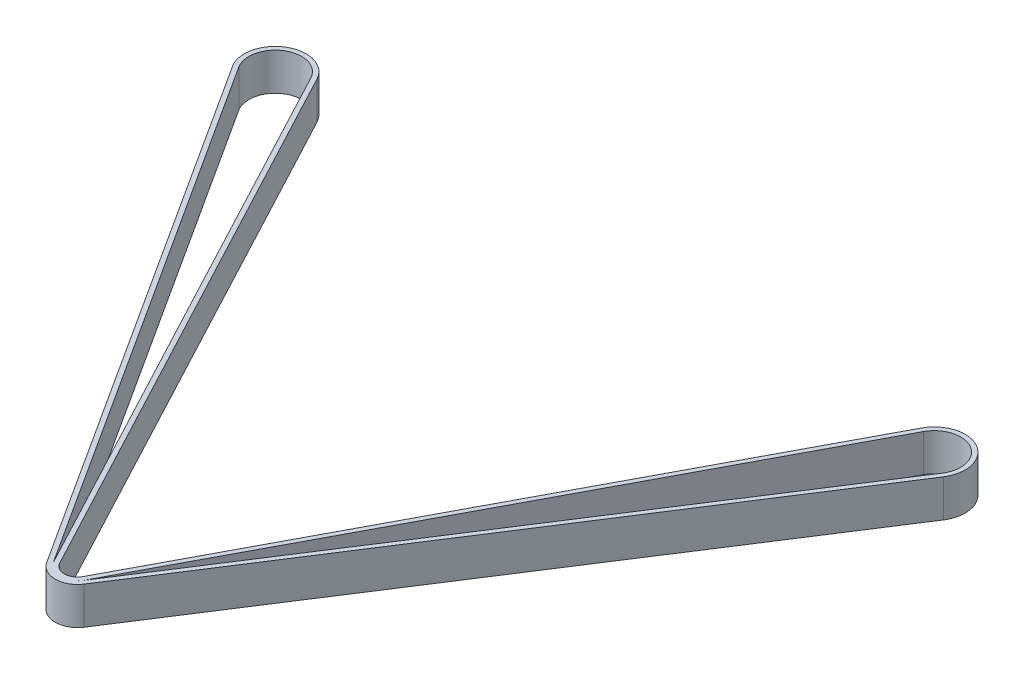
SolidWorks part; units mm, degrees
ref_plane "Front" through (0, 0, 0) normal (0, 0, 1) x (1, 0, 0)
ref_plane "Top" through (0, 0, 0) normal (0, 1, 0) x (1, 0, 0)
ref_plane "Right" through (0, 0, 0) normal (1, 0, 0) x (0, 0, -1)
ref_axis "X" through (-80.9, 0, 0) along (1, 0, 0)
ref_axis "Y" through (0, -50, 0) along (0, 1, 0)
ref_axis "Z" through (0, 0, -80.9) along (0, 0, 1)
sketch "Sketch1" plane through (0, 0, 0) normal (0, 1, 0) x (1, 0, 0)
  line L0 (-50, 0) -> (50, 0) construction
  line L1 (0, 0) -> (0, -80) construction
  line L2 (-46.1614, 2.0358) -> (-2.0717, -81.0987) construction
  line L3 (2.0717, -81.0987) -> (46.1614, 2.0358) construction
  line L4 (53.6522, -2.3537) -> (2.5519, -81.6446) construction
  line L5 (-2.5519, -81.6446) -> (-53.6522, -2.3537) construction
  line L6 (-2.8419, -81.8315) -> (-53.9422, -2.5406)
  line L7 (-45.8566, 2.1974) -> (-1.7669, -80.9371)
  line L8 (1.7669, -80.9371) -> (45.8566, 2.1974)
  line L9 (53.9422, -2.5406) -> (2.8419, -81.8315)
  line L10 (-2.262, -81.4578) -> (-53.3623, -2.1669)
  line L11 (-46.4662, 1.8741) -> (-2.3765, -81.2603)
  line L12 (2.3765, -81.2603) -> (46.4662, 1.8741)
  line L13 (53.3623, -2.1669) -> (2.262, -81.4578)
  line L14 (0, -82.69) -> (0, -82.691) construction
  circle A0 centre (-50, 0) radius 4 construction
  circle A1 centre (50, 0) radius 4 construction
  arc A2 (-46.1614, 2.0358) -> (-53.6522, -2.3537) centre (-50, 0) ccw construction
  arc A3 (53.6522, -2.3537) -> (46.1614, 2.0358) centre (50, 0) ccw construction
  circle A4 centre (0, -80) radius 2 construction
  arc A5 (-2.0717, -81.0987) -> (2.0717, -81.0987) centre (0, -80) ccw construction
  arc A6 (-2.5519, -81.6446) -> (2.5519, -81.6446) centre (0, -80) ccw construction
  arc A7 (-45.8566, 2.1974) -> (-53.9422, -2.5406) centre (-50, 0) ccw
  arc A8 (-1.7669, -80.9371) -> (1.7669, -80.9371) centre (0, -80) ccw
  arc A9 (53.9422, -2.5406) -> (45.8566, 2.1974) centre (50, 0) ccw
  arc A10 (-2.8419, -81.8315) -> (2.8419, -81.8315) centre (0, -80) ccw
  arc A11 (-46.4662, 1.8741) -> (-53.3623, -2.1669) centre (-50, 0) ccw
  arc A12 (-2.3765, -81.2603) -> (2.3765, -81.2603) centre (0, -80) ccw
  arc A13 (53.3623, -2.1669) -> (46.4662, 1.8741) centre (50, 0) ccw
  arc A14 (-2.262, -81.4578) -> (2.262, -81.4578) centre (0, -80) ccw
  dimension "D2" = 8
  dimension "D3" = 4
  dimension "D1" = 100
  dimension "D4" = 80
  dimension "D7" = 0.001
  dimension "D5" = 0.345
  dimension "D6" = 0.345
extrude "Boss-Extrude1" add sketch "Sketch1" along normal mid plane 5.67
